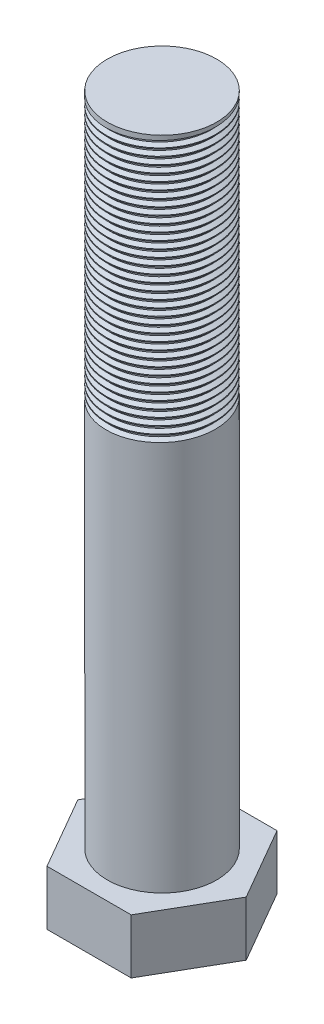
SolidWorks part; units mm, degrees
ref_plane "Front Plane" through (0, 0, 0) normal (0, 0, 1) x (1, 0, 0)
ref_plane "Top Plane" through (0, 0, 0) normal (0, 1, 0) x (1, 0, 0)
ref_plane "Right Plane" through (0, 0, 0) normal (1, 0, 0) x (0, 0, -1)
sketch "Sketch2" plane through (0, 0, 0) normal (0, 1, 0) x (1, 0, 0)
  line L1 (23.094, 0) -> (11.547, 20)
  line L2 (11.547, 20) -> (-11.547, 20)
  line L3 (-11.547, 20) -> (-23.094, 0)
  line L4 (-23.094, 0) -> (-11.547, -20)
  line L5 (-11.547, -20) -> (11.547, -20)
  line L6 (11.547, -20) -> (23.094, 0)
  circle A0 centre (0, 0) radius 20 construction
extrude "Boss-Extrude1" add sketch "Sketch2" along normal blind 15
sketch "Sketch3" plane through (0, 15, 0) normal (0, 1, 0) x (1, 0, 0)
  circle A0 centre (0, 0) radius 15
  dimension "D1" = 30
extrude "Boss-Extrude2" add sketch "Sketch3" along normal blind 180
thread "Thread1" pitch 2 method cut profile "Thread Profile1" start angle 0, offset 0, length 72, pitch 2, diameter 30
ref_plane "Plane1" through (-15, 195, 0) normal (0, 0, 1) x (-1, 0, 0)
sketch "Thread Profile1" plane through (-15, 195, 0) normal (0, 0, 1) x (-1, 0, 0)
  line L0 (0, 0) -> (0, 2) construction
  line L11 (0, 0) -> (0, 1.75)
  line L12 (0, 1.75) -> (-1.0825, 1.125)
  line L13 (-1.0825, 1.125) -> (-1.0825, 0.625)
  line L15 (-1.0825, 0.625) -> (0, 0)
  line L17 (-1.0825, 0.875) -> (0, 0.875) construction
  point P2 (0, 0)
  dimension "Pitch" = 2
  dimension "Profile_Angle" = 60
  dimension "Profile_Land" = 0.5
  dimension "Profile_Height" = 1.0825
